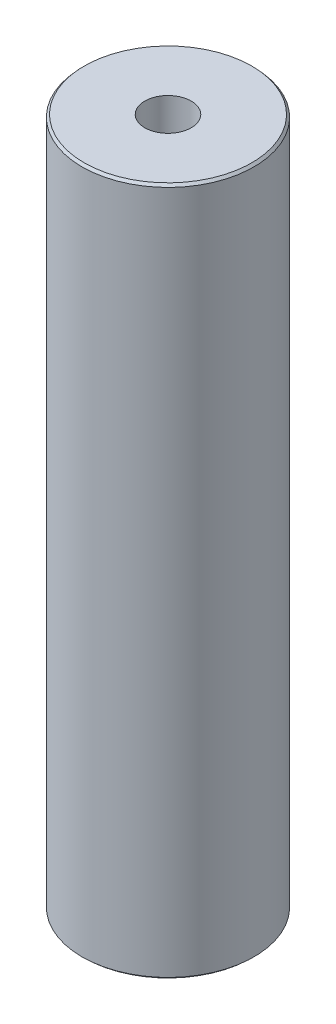
SolidWorks part; units mm, degrees
ref_plane "Front Plane" through (0, 0, 0) normal (0, 0, 1) x (1, 0, 0)
ref_plane "Top Plane" through (0, 0, 0) normal (0, 1, 0) x (1, 0, 0)
ref_plane "Right Plane" through (0, 0, 0) normal (1, 0, 0) x (0, 0, -1)
sketch "Sketch1" plane through (0, 0, 0) normal (0, 1, 0) x (1, 0, 0)
  circle A0 centre (0, 0) radius 10
  dimension "SHAFT_OD" = 20
extrude "Boss-Extrude1" add sketch "Sketch1" along normal blind 80.0774
sketch "Sketch2" plane through (0, 0, 0) normal (0, 1, 0) x (1, 0, 0)
  circle A0 centre (0, 0) radius 2.6972
  dimension "BORE_D" = 5.3945
extrude "Cut-Extrude1" cut sketch "Sketch2" along normal through all
chamfer "Chamfer1" distance 0.2823 angle 42.076 2 edges at (0, 80.0774, 10) (0, 0, 10) first distance on face at (0, 80.0774, 10) first distance on face at (0, 0, 2.6972)
